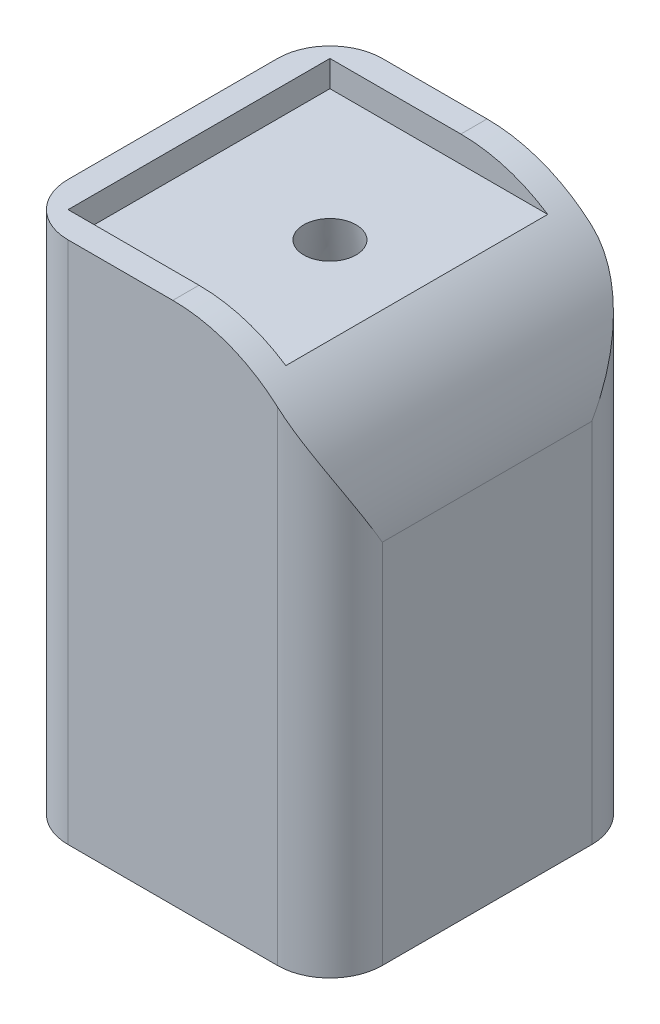
SolidWorks part; units mm, degrees
ref_plane "Front Plane" through (0, 0, 0) normal (0, 0, 1) x (1, 0, 0)
ref_plane "Top Plane" through (0, 0, 0) normal (0, 1, 0) x (1, 0, 0)
ref_plane "Right Plane" through (0, 0, 0) normal (1, 0, 0) x (0, 0, -1)
sketch "Sketch2" plane through (0, 0, 0) normal (0, 1, 0) x (1, 0, 0)
  line L1 (-15, -15) -> (15, -15)
  line L2 (-15, -15) -> (-15, 15)
  line L3 (-15, 15) -> (15, 15)
  line L4 (15, -15) -> (15, 15)
  line L5 (0, 15) -> (0, -15) construction
  line L6 (-15, 0) -> (15, 0) construction
  point P0 (0, 0)
  dimension "D1" = 30
  dimension "D2" = 30
extrude "Boss-Extrude1" add sketch "Sketch2" along normal blind 50
sketch "Sketch3" plane through (0, 50, 0) normal (0, 1, 0) x (1, 0, 0)
  line L1 (-12.5, -12.5) -> (12.5, -12.5)
  line L2 (-12.5, -12.5) -> (-12.5, 12.5)
  line L3 (-12.5, 12.5) -> (12.5, 12.5)
  line L4 (12.5, -12.5) -> (12.5, 12.5)
  line L5 (0, 12.5) -> (0, -12.5) construction
  line L6 (-12.5, 0) -> (12.5, 0) construction
  point P0 (0, 0)
  dimension "D1" = 25
  dimension "D2" = 25
extrude "Cut-Extrude1" cut sketch "Sketch3" against normal blind 2.5
fillet "Fillet1" radius 5 4 edges at (15, 25, 15) (15, 25, -15) (-15, 25, -15) (-15, 25, 15)
sketch "Sketch6" plane through (0, 0, 0) normal (0, -1, 0) x (1, 0, 0)
  circle A0 centre (0, 0) radius 12.5
  dimension "D1" = 25
sketch "Sketch8" plane through (0, 47.5, 0) normal (0, 1, 0) x (1, 0, 0)
  circle A0 centre (0, 0) radius 2.5
  dimension "D1" = 5
loft "Cut-Loft2" cut profiles "Sketch6", "Sketch8" connector at (0, 0, -12.5) connector at (0.7845, 47.5, -2.3737)
sketch "Sketch9" plane through (0, 0, 15) normal (0, 0, 1) x (1, 0, 0)
  line L0 (0, 0) -> (0, 50) construction
  line L1 (-10, 0) -> (10, 0) construction
  line L2 (-10, 50) -> (10, 50) construction
  line L3 (0, 50) -> (15, 50)
  line L4 (15, 50) -> (15, 35)
  circle A0 centre (0, 35) radius 15
  point P2 (15, 50)
  line M5 (10, 0) -> (10, 50)
  line M6 (10, 50) -> (-10, 50)
  dimension "D1" = 15
  dimension "D2" = 30
extrude "Cut-Extrude2" cut sketch "Sketch9" against normal through all contours A0 L4 L3 M5 | A0 M5 M6 region at (7.5681, 48.8843, 15) region at (12.9998, 45.9101, 15)
